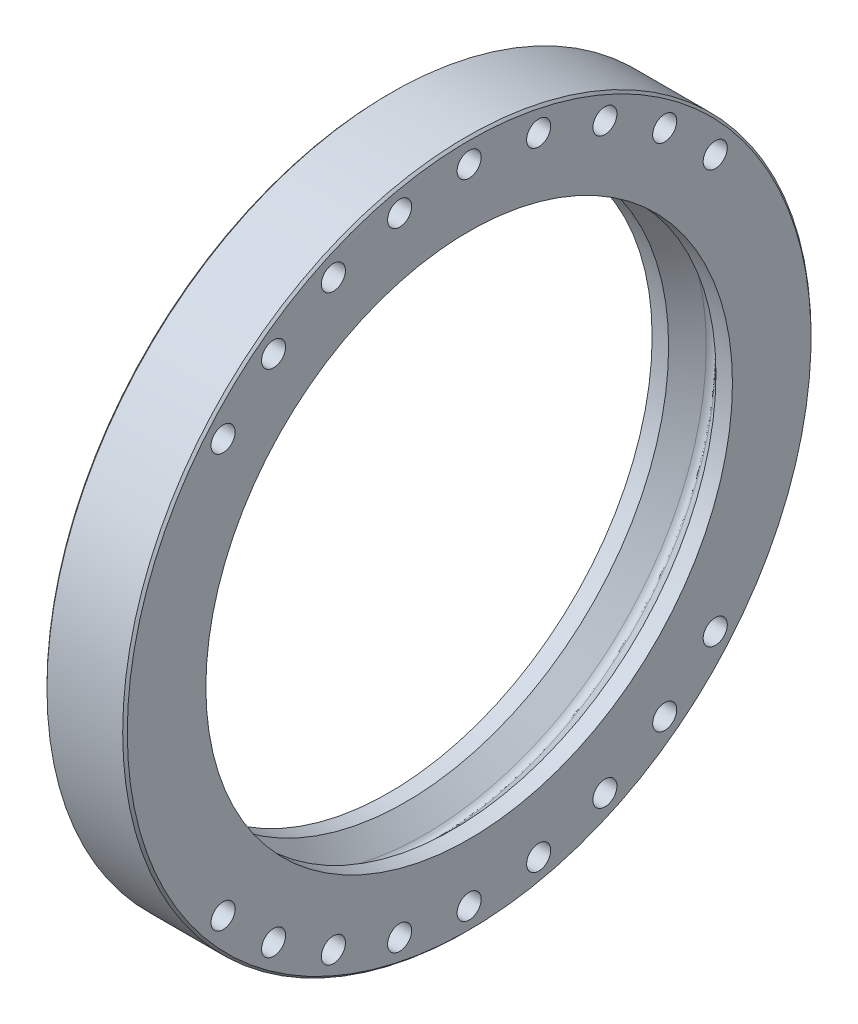
SolidWorks part; units mm, degrees
ref_plane "Front Plane" through (0, 0, 0) normal (0, 0, 1) x (1, 0, 0)
ref_plane "Top Plane" through (0, 0, 0) normal (0, 1, 0) x (1, 0, 0)
ref_plane "Right Plane" through (0, 0, 0) normal (1, 0, 0) x (0, 0, -1)
sketch "Sketch1" plane through (0, 0, 0) normal (0, 0, 1) x (1, 0, 0)
  line L0 (0, 0) -> (-227.5, 0) construction
  line L1 (0, 132.375) -> (0, 80.0238) construction
  line L2 (17.5, 150) -> (-17.5, 150)
  line L3 (17.5, 150) -> (17.5, 114.75)
  line L4 (17.5, 114.75) -> (-17.5, 114.75)
  line L5 (-17.5, 150) -> (-17.5, 114.75)
  line L6 (17.5, 150) -> (-17.5, 114.75) construction
  line L7 (17.5, 114.75) -> (-17.5, 150) construction
  line L8 (0, 125.0637) -> (11.3137, 113.75)
  line L9 (0, 125.0637) -> (-11.3137, 113.75)
  line L10 (11.3137, 113.75) -> (0, 102.4363)
  line L11 (-11.3137, 113.75) -> (0, 102.4363)
  line L12 (0, 125.0637) -> (0, 102.4363) construction
  line L13 (11.3137, 113.75) -> (-11.3137, 113.75) construction
  circle A0 centre (0, 113.75) radius 8 construction
  point P3 (0, 132.375)
  point P9 (0, 113.75)
  dimension "D5" = 16
  dimension "D1" = 114.75
  dimension "D2" = 150
  dimension "D3" = 35
  dimension "D4" = 113.75
revolve "Revolve1" add sketch "Sketch1" angle 360 about L0 region at (0, 133.7136, 0)
chamfer "Chamfer1" distance 1 angle 45 2 edges at (17.5, 0, -150) (-17.5, 0, -150)
fillet "Fillet1" radius 3 1 edges at (0, 0, -125.0637) curvature continuous yes
ref_axis "Axis1" through (-16.5, 0, 0) along (1, 0, 0)
sketch "Sketch2" plane through (-17.5, 0, 0) normal (-1, 0, 0) x (0, 0, 1)
  line L0 (0, 0) -> (0, 140) construction
  circle A0 centre (0, 0) radius 140 construction
  dimension "D1" = 280
hole_wizard "CBORE for M10 Hex Head Bolt2" positions "3DSketch2" profile "Sketch3" counterbore size "M10" standard "ISO" end condition through all
sketch3d "3DSketch2"
  point P0 (-17.5, 140, 0)
sketch "Sketch3" plane through (-17.5, 140, 0) normal (0, 1, 0) x (0, 0, 1)
  line L0 (0, 0) -> (0, 35)
  line L1 (0, 35) -> (5.25, 35)
  line L3 (5.25, 35) -> (5.25, 10.8)
  line L4 (5.25, 10.8) -> (8, 10.8)
  line L5 (8, 10.8) -> (8, 0)
  line L7 (8, 0) -> (0, 0)
  line L11 (0, -6.35) -> (0, 107.95) construction
  dimension "Thru Hole Dia." = 10.5
  dimension "Thru Hole Depth" = 35
  dimension "C'Bore Dia." = 16
  dimension "C'Bore Depth" = 10.8
pattern_circular "CirPattern1" count 5 every 12.5 about axis through (-16.5, 0, 0) along (1, 0, 0) of "CBORE for M10 Hex Head Bolt2" other way count 5
mirror "Mirror1" about plane through (0, 0, 0) normal (0, 1, 0) of "CirPattern1"
